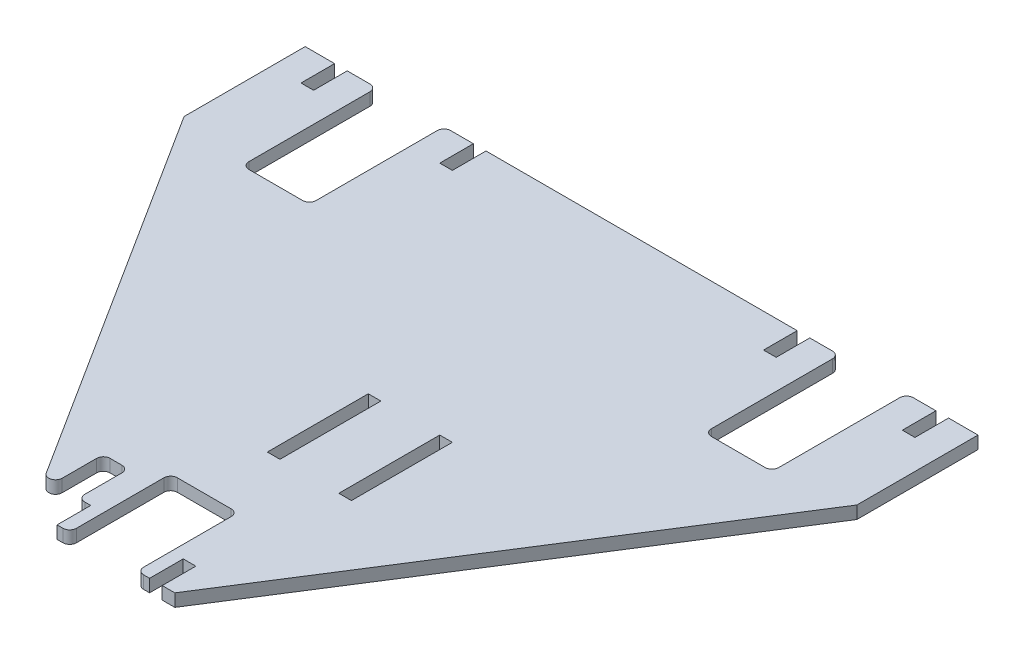
SolidWorks part; units mm, degrees
material "Corrugated Paper"
ref_plane "Front Plane" through (0, 0, 0) normal (0, 0, 1) x (1, 0, 0)
ref_plane "Top Plane" through (0, 0, 0) normal (0, 1, 0) x (1, 0, 0)
ref_plane "Right Plane" through (0, 0, 0) normal (1, 0, 0) x (0, 0, -1)
sketch "Sketch1" plane through (0, 0, 0) normal (0, 1, 0) x (1, 0, 0)
  line L0 (0, 0) -> (0, -142.875) construction
  line L1 (12.7, -63.5) -> (-12.7, -63.5)
  line L2 (-12.7, -63.5) -> (-12.7, -101.6)
  line L3 (-12.7, -101.6) -> (-17.4625, -101.6)
  line L4 (-26.9875, -101.6) -> (-127, 55.88)
  line L5 (-127, 55.88) -> (-127, 101.6)
  line L6 (-127, 101.6) -> (-115.8875, 101.6)
  line L7 (-100.0125, 101.6) -> (-100.0125, 50.8)
  line L9 (-100.0125, 50.8) -> (-74.6125, 50.8)
  line L10 (-74.6125, 50.8) -> (-74.6125, 101.6)
  line L11 (-74.6125, 101.6) -> (-63.5, 101.6)
  line L13 (74.6125, 50.8) -> (74.6125, 101.6)
  line L14 (100.0125, 50.8) -> (74.6125, 50.8)
  line L15 (100.0125, 101.6) -> (100.0125, 50.8)
  line L16 (127, 101.6) -> (115.8875, 101.6)
  line L17 (127, 55.88) -> (127, 101.6)
  line L18 (26.9875, -101.6) -> (127, 55.88)
  line L19 (12.7, -101.6) -> (17.4625, -101.6)
  line L20 (12.7, -63.5) -> (12.7, -101.6)
  line L21 (-127, 101.6) -> (127, -101.6) construction
  line L22 (-22.225, -101.6) -> (-26.9875, -101.6)
  line L24 (-22.225, -101.6) -> (-22.225, -88.9)
  line L25 (-22.225, -88.9) -> (-17.4625, -88.9)
  line L26 (-17.4625, -101.6) -> (-17.4625, -88.9)
  line L27 (22.225, -101.6) -> (22.225, -88.9)
  line L28 (22.225, -88.9) -> (17.4625, -88.9)
  line L29 (17.4625, -101.6) -> (17.4625, -88.9)
  line L30 (22.225, -101.6) -> (26.9875, -101.6)
  line L31 (-87.3125, 50.8) -> (-87.3125, 101.6) construction
  line L32 (-111.125, 101.6) -> (-100.0125, 101.6)
  line L34 (-115.8875, 101.6) -> (-115.8875, 88.9)
  line L35 (-115.8875, 88.9) -> (-111.125, 88.9)
  line L36 (-111.125, 101.6) -> (-111.125, 88.9)
  line L37 (-58.7375, 101.6) -> (-58.7375, 88.9)
  line L38 (-58.7375, 88.9) -> (-63.5, 88.9)
  line L39 (-63.5, 101.6) -> (-63.5, 88.9)
  line L40 (-58.7375, 101.6) -> (58.7375, 101.6)
  line L41 (115.8875, 101.6) -> (115.8875, 88.9)
  line L42 (115.8875, 88.9) -> (111.125, 88.9)
  line L43 (111.125, 101.6) -> (111.125, 88.9)
  line L44 (58.7375, 101.6) -> (58.7375, 88.9)
  line L45 (63.5, 101.6) -> (63.5, 88.9)
  line L46 (58.7375, 88.9) -> (63.5, 88.9)
  line L47 (63.5, 101.6) -> (74.6125, 101.6)
  line L48 (111.125, 101.6) -> (100.0125, 101.6)
  point P26 (0, -63.5)
  dimension "D2" = 25.4
  dimension "D3" = 254
  dimension "D5" = 38.1
  dimension "D6" = 50.8
  dimension "D7" = 203.2
  dimension "D8" = 45.72
  dimension "D9" = 26.9875
  dimension "D4" = 14.2875
  dimension "D10" = 4.7625
  dimension "D11" = 12.7
  dimension "D12" = 4.7625
extrude "Boss-Extrude1" add sketch "Sketch1" along normal blind 4.7625 contours L13 L47 L45 L46 L44 L40 L37 L38 L39 L11 L10 L9 L7 L32 L36 L35 L34 L6 L5 L4 L22 L24 L25 L26 L3 L2 L1 L20 L19 L29 L28 L27 L30 L18 L17 L16 L41 L42 L43 L48 L15 L14
sketch "Sketch2" plane through (0, 4.7625, 0) normal (0, 1, 0) x (1, 0, 0)
  line L0 (14.2875, 0) -> (14.2875, 54.8341) construction
  line L6 (-58.7375, 88.9) -> (-63.5, 88.9) construction
  line L7 (-1.5875, 0) -> (3.175, 0)
  line L8 (-1.5875, 0) -> (-1.5875, -38.1)
  line L9 (-1.5875, -38.1) -> (3.175, -38.1)
  line L10 (3.175, 0) -> (3.175, -38.1)
  line L11 (-22.225, -101.6) -> (-31.75, -101.6)
  line L12 (25.4, 0) -> (25.4, -38.1)
  line L13 (30.1625, -38.1) -> (25.4, -38.1)
  line L14 (30.1625, 0) -> (30.1625, -38.1)
  line L15 (30.1625, 0) -> (25.4, 0)
  line L16 (-22.225, -101.6) -> (-22.225, -69.85)
  line L17 (12.7, -63.5) -> (-12.7, -63.5) construction
  line L18 (-22.225, -69.85) -> (-31.75, -69.85)
  line L19 (-31.75, -101.6) -> (-31.75, -69.85)
  dimension "D2" = 25.4
  dimension "D4" = 14.2875
  dimension "D3" = 31.75
  dimension "D1" = 38.1
  dimension "D5" = 9.525
  dimension "D6" = 31.75
extrude "Cut-Extrude1" cut sketch "Sketch2" against normal through all
fillet "Fillet1" radius 2.54 4 edges at (-22.225, 2.3813, 88.9) (-31.75, 2.3813, 94.101) (-22.225, 2.3813, 69.85) (-31.75, 2.3813, 69.85)
fillet "Fillet2" radius 2.54 12 edges at (-12.7, 2.3813, 101.6) (12.7, 2.3813, 101.6) (12.7, 2.3813, 63.5) (-12.7, 2.3813, 63.5) (100.0125, 2.3813, -101.6) (100.0125, 2.3813, -50.8) (74.6125, 2.3813, -101.6) (74.6125, 2.3813, -50.8) (-100.0125, 2.3813, -101.6) (-74.6125, 2.3813, -101.6) (-74.6125, 2.3813, -50.8) (-100.0125, 2.3813, -50.8)
equation "\"D1@Boss-Extrude1\" = \"thick\""
equation "\"D4@Sketch1\" = \"thick\" * 3"
equation "\"D10@Sketch1\" = \"thick\""
equation "\"D9@Sketch1\" = \"thick\" * 3 + 0.5"
equation "\"D12@Sketch1\" = \"thick\""
equation "\"D3@Sketch2\"=\"MotorLength@Motor-1.Part\""
equation "\"D1@Sketch2\" =  ( \"MotorDiameter@Motor-1.Part\" + 0.5 ) "
equation "\"D4@Sketch2\"= 3 * \"thick\""
equation "\"rodThick\"= 0.1in"
equation "\"thick\"= 3 / 16"
equation "\"D5@Sketch2\"=2*\"thick\""
